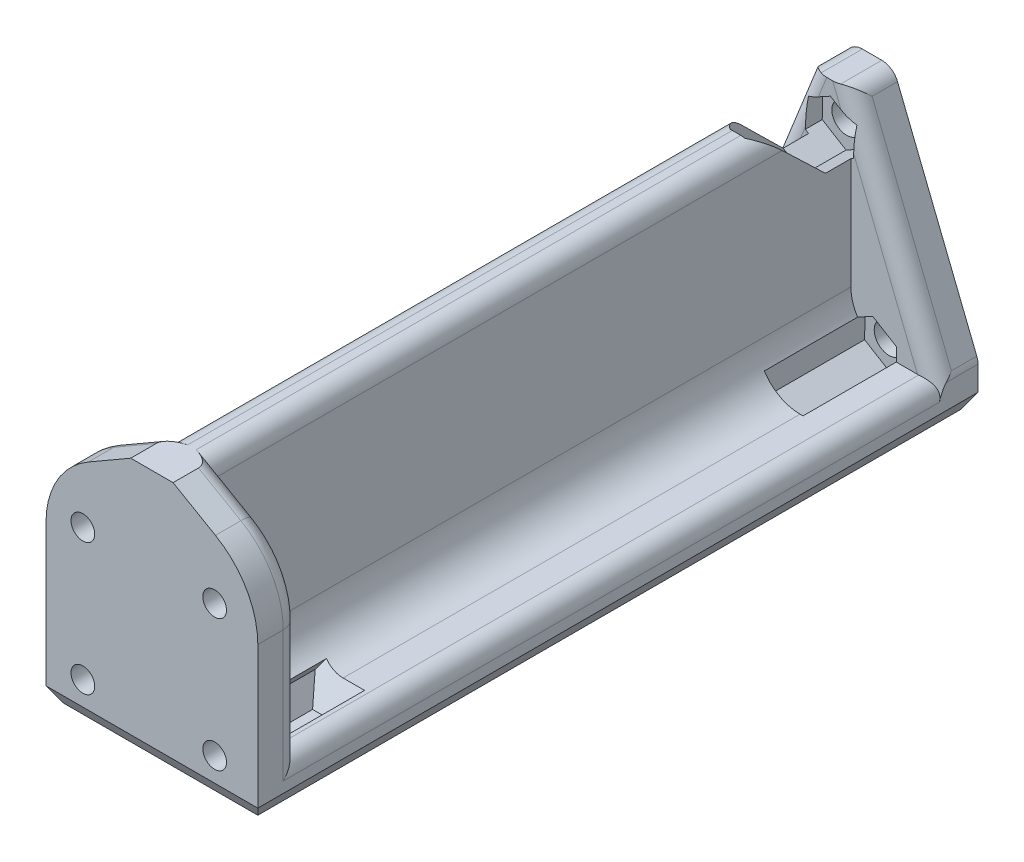
SolidWorks part; units mm, degrees
ref_plane "Front Plane" through (0, 0, 0) normal (0, 0, 1) x (1, 0, 0)
ref_plane "Top Plane" through (0, 0, 0) normal (0, 1, 0) x (1, 0, 0)
ref_plane "Right Plane" through (0, 0, 0) normal (1, 0, 0) x (0, 0, -1)
sketch "Sketch1" plane through (0, 0, 0) normal (0, 0, 1) x (1, 0, 0)
  line L0 (0, 0) -> (25, 0)
  line L1 (0, 0) -> (0, 5)
  line L2 (0, 5) -> (10, 5)
  line L3 (10, 5) -> (10, 30)
  line L4 (10, 30) -> (15, 30)
  line L5 (15, 30) -> (15, 5)
  line L6 (15, 5) -> (25, 5)
  line L7 (25, 5) -> (25, 0)
  dimension "D1" = 5
  dimension "D2" = 5
  dimension "D3" = 5
  dimension "D4" = 25
  dimension "D5" = 10
  dimension "D6" = 10
  dimension "D7" = 25
extrude "Boss-Extrude1" add sketch "Sketch1" against normal blind 75
fillet "Fillet3" radius 5 2 edges at (15, 5, -37.5) (10, 5, -37.5)
fillet "Fillet4" radius 2 4 edges at (25, 5, -37.5) (0, 5, -37.5) (15, 30, -37.5) (10, 30, -37.5)
sketch "Sketch4" plane through (0, 0, -75) normal (0, 0, -1) x (-1, 0, 0)
  line L0 (-25, 5) -> (-15, 30)
  line L1 (-15, 30) -> (-10, 30)
  line L2 (-10, 30) -> (0, 5)
  line L3 (0, 5) -> (0, 0)
  line L4 (0, 0) -> (-25, 0)
  line L5 (-25, 0) -> (-25, 5)
  dimension "D1" = 5
  dimension "D2" = 5
  dimension "D3" = 5
  dimension "D4" = 26.9258
  dimension "D5" = 26.9258
extrude "Boss-Extrude3" add sketch "Sketch4" along normal blind 5
sketch "Sketch6" plane through (0, 0, -80) normal (0, 0, -1) x (-1, 0, 0)
  line L0 (-10, 30) -> (-15, 30) construction
  circle A0 centre (-12.5, 25) radius 1.75
  circle A1 centre (-7.5, 5) radius 1.75
  circle A2 centre (-17.5, 5) radius 1.75
  dimension "D1" = 3.5
  dimension "D2" = 3.5
  dimension "D4" = 3.5
  dimension "D3" = 0
  dimension "D5" = 5
  dimension "D6" = 2.5
  dimension "D7" = 10
  dimension "D8" = 5
  dimension "D9" = 20
extrude "Cut-Extrude2" cut sketch "Sketch6" against normal blind 10
sketch "Sketch7" plane through (0, 0, -80) normal (0, 0, -1) x (-1, 0, 0)
  line L1 (-14.6877, 6.7091) -> (-17.574, 8.2901)
  line L2 (-17.574, 8.2901) -> (-20.3863, 6.5809)
  line L3 (-20.3863, 6.5809) -> (-20.3123, 3.2909)
  line L4 (-20.3123, 3.2909) -> (-17.426, 1.7099)
  line L5 (-17.426, 1.7099) -> (-14.6137, 3.4191)
  line L6 (-14.6137, 3.4191) -> (-14.6877, 6.7091)
  line L7 (-4.6877, 6.7091) -> (-7.574, 8.2901)
  line L8 (-7.574, 8.2901) -> (-10.3863, 6.5809)
  line L9 (-10.3863, 6.5809) -> (-10.3123, 3.2909)
  line L10 (-10.3123, 3.2909) -> (-7.426, 1.7099)
  line L11 (-7.426, 1.7099) -> (-4.6137, 3.4191)
  line L12 (-4.6137, 3.4191) -> (-4.6877, 6.7091)
  line L13 (-9.6877, 26.7091) -> (-12.574, 28.2901)
  line L14 (-12.574, 28.2901) -> (-15.3863, 26.5809)
  line L15 (-15.3863, 26.5809) -> (-15.3123, 23.2909)
  line L16 (-15.3123, 23.2909) -> (-12.426, 21.7099)
  line L17 (-12.426, 21.7099) -> (-9.6137, 23.4191)
  line L18 (-9.6137, 23.4191) -> (-9.6877, 26.7091)
  circle A0 centre (-17.5, 5) radius 2.85 construction
  circle A1 centre (-7.5, 5) radius 2.85 construction
  circle A2 centre (-12.5, 25) radius 2.85 construction
  dimension "D1" = 5.7
  dimension "D2" = 5.7
  dimension "D3" = 5.7
extrude "Cut-Extrude3" cut sketch "Sketch7" against normal blind 13 from offset 3 offset against normal yes
sketch "Sketch8" plane through (0, 0, 0) normal (0, 0, 1) x (1, 0, 0)
  line L1 (0, 0) -> (25, 0)
  line L2 (0, 0) -> (0, 30)
  line L3 (0, 30) -> (25, 30)
  line L4 (25, 0) -> (25, 30)
  dimension "D1" = 25
  dimension "D2" = 30
extrude "Boss-Extrude4" add sketch "Sketch8" along normal blind 5
sketch "Sketch9" plane through (0, 0, 5) normal (0, 0, 1) x (1, 0, 0)
  line L1 (0, 0) -> (25, 0) construction
  line L2 (12.5, 30) -> (12.5, 0) construction
  line L3 (25, 30) -> (0, 30) construction
  circle A0 centre (4.35, 4.55) radius 1.4
  circle A1 centre (19.9063, 4.55) radius 1.4
  circle A2 centre (19.9063, 20.1063) radius 1.4
  circle A3 centre (4.35, 20.1063) radius 1.4
  dimension "D1" = 2.8
  dimension "D2" = 2.8
  dimension "D3" = 2.8
  dimension "D4" = 2.8
  dimension "D8" = 15.5563
  dimension "D5" = 0
  dimension "D6" = 0
  dimension "D7" = 0
  dimension "D9" = 15.5563
  dimension "D10" = 15.5563
  dimension "D11" = 4.55
  dimension "D12" = 8.15
extrude "Cut-Extrude4" cut sketch "Sketch9" against normal up to surface (5 mm away) up to face at (19.399, 15.8276, 0)
sketch "Sketch10" plane through (0, 0, 5) normal (0, 0, 1) x (1, 0, 0)
  line L1 (7.2368, 4.55) -> (5.7934, 7.05)
  line L2 (5.7934, 7.05) -> (2.9066, 7.05)
  line L3 (2.9066, 7.05) -> (1.4632, 4.55)
  line L4 (1.4632, 4.55) -> (2.9066, 2.05)
  line L5 (2.9066, 2.05) -> (5.7934, 2.05)
  line L6 (5.7934, 2.05) -> (7.2368, 4.55)
  line L7 (22.7931, 4.55) -> (21.3497, 7.05)
  line L8 (21.3497, 7.05) -> (18.463, 7.05)
  line L9 (18.463, 7.05) -> (17.0196, 4.55)
  line L10 (17.0196, 4.55) -> (18.463, 2.05)
  line L11 (18.463, 2.05) -> (21.3497, 2.05)
  line L12 (21.3497, 2.05) -> (22.7931, 4.55)
  line L13 (7.2368, 20.1063) -> (5.7934, 22.6063)
  line L14 (5.7934, 22.6063) -> (2.9066, 22.6063)
  line L15 (2.9066, 22.6063) -> (1.4632, 20.1063)
  line L16 (1.4632, 20.1063) -> (2.9066, 17.6063)
  line L17 (2.9066, 17.6063) -> (5.7934, 17.6063)
  line L18 (5.7934, 17.6063) -> (7.2368, 20.1063)
  line L19 (22.7931, 20.1063) -> (21.3497, 22.6063)
  line L20 (21.3497, 22.6063) -> (18.463, 22.6063)
  line L21 (18.463, 22.6063) -> (17.0196, 20.1063)
  line L22 (17.0196, 20.1063) -> (18.463, 17.6063)
  line L23 (18.463, 17.6063) -> (21.3497, 17.6063)
  line L24 (21.3497, 17.6063) -> (22.7931, 20.1063)
  circle A0 centre (4.35, 4.55) radius 2.5 construction
  circle A1 centre (19.9063, 4.55) radius 2.5 construction
  circle A2 centre (4.35, 20.1063) radius 1.4 construction
  circle A3 centre (19.9063, 20.1063) radius 1.4 construction
  circle A4 centre (4.35, 20.1063) radius 1.4 construction
  circle A5 centre (19.9063, 20.1063) radius 1.4 construction
  circle A6 centre (4.35, 20.1063) radius 2.5 construction
  circle A7 centre (19.9063, 20.1063) radius 2.5 construction
  dimension "D3" = 5
  dimension "D4" = 5
extrude "Cut-Extrude5" cut sketch "Sketch10" against normal blind 13 from offset 3 offset against normal yes
chamfer "Chamfer1" distance 3 angle 55 2 edges at (19.9063, 2.05, -11) (4.35, 2.05, -11) first distance on face at (19.9063, 2.05, -4.5) first distance on face at (4.35, 2.05, -4.5)
chamfer "Chamfer2" distance 10 angle 30 2 edges at (25, 30, 2.5) (0, 30, 2.5) first distance on face at (12.5, 30, -37.5)
fillet "Fillet5" radius 10 2 edges at (0, 24.2265, 2.5) (25, 24.2265, 2.5)
sketch "Sketch11" plane through (15, 0, 0) normal (1, 0, 0) x (0, 0, -1)
  line L0 (64, 23.1198) -> (64, 26.8157) construction
  line L1 (75, 30) -> (64, 30)
  line L2 (75, 30) -> (75, 24.9678)
  line L3 (75, 24.9678) -> (64, 24.9678)
  line L4 (64, 30) -> (64, 24.9678)
extrude "Cut-Extrude6" cut sketch "Sketch11" against normal up to surface (5 mm away) up to face at (10, 22.0161, -53.5)
fillet "Fillet6" radius 2 12 edges at (17.5, 28.5566, 0) (23.6603, 23.453, 0) (7.5, 28.5566, 0) (1.3397, 23.453, 0) (25, 10.7265, 0) (0, 10.7265, 0) (0, 5, -77.5) (25, 5, -77.5) (10, 30, -77.5) (15, 30, -77.5) (5, 17.5, -75) (20, 17.5, -75)
chamfer "Chamfer3" distance 8 angle 40 2 edges at (11.213, 22.4471, -64) (13.713, 22.4149, -64) first distance on face at (10.6799, 22.7711, -72) first distance on face at (14.2461, 22.7069, -72)
chamfer "Chamfer4" distance 1 angle 60 4 edges at (12.5, 0, -80) (0, 0, -37.5) (12.5, 0, 5) (25, 0, -37.5) first distance on face at (12.5, 0, -37.5)
sketch "Sketch12" plane through (0, 5, 0) normal (0, 1, 0) x (1, 0, 0)
  line L0 (0.143, 80) -> (9.4971, 80) construction
  line L1 (0.143, 80) -> (9.4971, 80)
  line L2 (10, -5) -> (5, -5) construction
  line L3 (10, -5) -> (5, -5)
  line L4 (5, -5) -> (5, 80)
  line L5 (5, 37.5) -> (44.2601, 37.5)
ref_plane "Plane1" through (0, 0, -37.5) normal (0, 0, 1) x (1, 0, 0)
sketch "Sketch13" plane through (0, 0, 5) normal (0, 0, 1) x (1, 0, 0)
  circle A0 centre (19.9063, 20.1063) radius 1.4 construction
  circle A1 centre (19.9063, 4.55) radius 1.4 construction
  circle A2 centre (4.35, 20.1063) radius 1.4 construction
  circle A3 centre (4.35, 4.55) radius 1.4 construction
  circle A4 centre (19.9063, 20.1063) radius 1.4
  circle A5 centre (19.9063, 4.55) radius 1.4
  circle A6 centre (4.35, 20.1063) radius 1.4
  circle A7 centre (4.35, 4.55) radius 1.4
